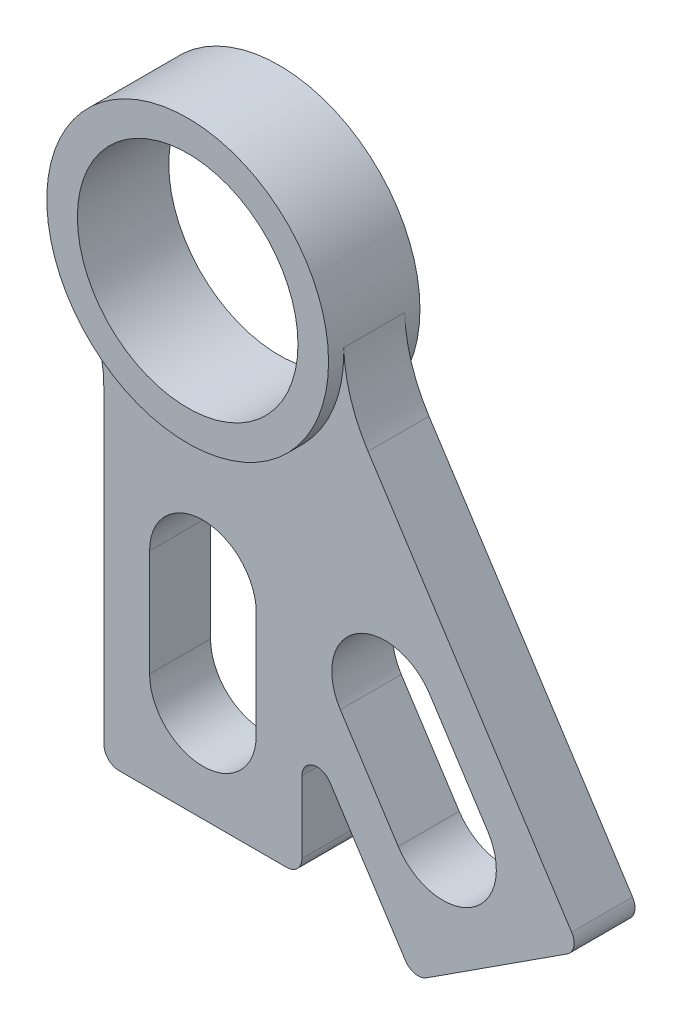
SolidWorks part; units mm, degrees
material "AISI 4130 Steel, annealed at 865C"
ref_plane "X-Y Datum" through (0, 0, 0) normal (0, 0, 1) x (1, 0, 0)
ref_plane "X-Z Datum" through (0, 0, 0) normal (0, 1, 0) x (1, 0, 0)
ref_plane "Y-Z Datum" through (0, 0, 0) normal (1, 0, 0) x (0, 0, -1)
sketch "Sketch1" plane through (0, 0, 0) normal (0, 0, 1) x (1, 0, 0)
  line L0 (0, -39.0706) -> (0, -27.9581) construction
  line L1 (-5.5562, -39.0706) -> (-5.5562, -27.9581)
  line L2 (5.5562, -39.0706) -> (5.5562, -27.9581)
  line L3 (25.0228, -38.6649) -> (18.9852, -29.3357) construction
  line L4 (20.3582, -41.6837) -> (14.3206, -32.3545)
  line L5 (29.6874, -35.6461) -> (23.6498, -26.3169)
  line L6 (-10.3187, -15.7343) -> (-10.3187, -49.3893)
  line L7 (-10.3187, -49.3893) -> (10.3187, -49.3893)
  line L10 (21.9663, -52.9341) -> (39.292, -41.7214)
  line L11 (39.292, -41.7214) -> (17.2116, -7.603)
  line L14 (0, -44.6268) -> (0, -49.3893) construction
  line L15 (28.0416, -43.3295) -> (30.6292, -47.3278) construction
  line L16 (26.6686, -30.9815) -> (30.6669, -28.3939) construction
  line L17 (-5.5562, -33.5143) -> (-10.3187, -33.5143) construction
  line L18 (-10.3187, -17.6393) -> (10.3187, -17.6393) construction
  line L19 (10.3187, -17.6393) -> (10.3187, -49.3893) construction
  line L20 (5.5562, -33.5143) -> (10.3187, -33.5143) construction
  line L21 (0, -22.4018) -> (0, -17.6393) construction
  line L22 (21.9663, -52.9341) -> (4.716, -26.2791) construction
  line L23 (4.716, -26.2791) -> (22.0417, -15.0664) construction
  line L24 (17.3394, -37.0191) -> (13.3411, -39.6066) construction
  line L25 (15.9664, -24.671) -> (13.3788, -20.6728) construction
  line L30 (21.9663, -52.9341) -> (10.3187, -34.9365)
  line L32 (10.3187, -34.9365) -> (10.3187, -49.3893)
  line L34 (218.5438, -337.6911) -> (0, 0) construction
  line L35 (0, -404.7476) -> (0, 0) construction
  circle A0 centre (0, 0) radius 11.4954
  arc A1 (-5.5562, -39.0706) -> (5.5562, -39.0706) centre (0, -39.0706) ccw
  arc A2 (5.5562, -27.9581) -> (-5.5562, -27.9581) centre (0, -27.9581) ccw
  arc A3 (20.3582, -41.6837) -> (29.6874, -35.6461) centre (25.0228, -38.6649) ccw
  arc A4 (23.6498, -26.3169) -> (14.3206, -32.3545) centre (18.9852, -29.3357) ccw
  arc A5 (14.673, 0.4911) -> (-12.5852, -7.5598) centre (0, 0) ccw
  arc A6 (17.2116, -7.603) -> (14.673, 0.4911) centre (30.5391, 1.0221) cw
  arc A7 (-10.3187, -15.7343) -> (-12.5852, -7.5598) centre (-26.1937, -15.7343) ccw
  arc A14 (-12.5852, -7.5598) -> (14.673, 0.4911) centre (0, 0) ccw
  point P5 (0, -33.5143)
  point P11 (22.004, -34.0003)
  point P24 (30.6292, -47.3278)
  point P31 (0, -49.3893)
  point P39 (28.0416, -43.3295)
  dimension "D1" = 22.9908
  dimension "D2" = 14.6812
  dimension "D8" = 15.875
  dimension "D3" = 20.6375
  dimension "D4" = 4.7625
  dimension "D5" = 31.75
  dimension "D6" = 8.89
  dimension "D7" = 1.905
extrude "Boss-Extrude2" add sketch "Sketch1" along normal mid plane 9.525 contours A5 A14 A0 region at (-4.041, 13.6817, 0)
extrude "Boss-Extrude3" add sketch "Sketch1<4>" along normal mid plane 6.35 contours A14 A7 L6 L7 L10 L11 A6 A4 L5 A3 L4 A2 L2 A1 L1 region at (10.5595, -29.9499, 0)
sketch "Sketch1<4>" plane through (0, 0, 0) normal (0, 0, 1) x (1, 0, 0) same geometry as "Sketch1"
fillet "Fillet1" radius 1.5875 5 edges at (-10.3187, -49.3893, 0) (39.292, -41.7214, 0) (10.3187, -49.3893, 0) (21.9663, -52.9341, 0) (10.3187, -34.9365, 0)
sketch "Sketch2" plane through (0, 0, 4.7625) normal (0, 0, 1) x (1, 0, 0)
  point P0 (0, 0)
sketch "Sketch3" plane through (0, 0, -4.7625) normal (0, 0, -1) x (-1, 0, 0)
  point P0 (0, 0)
